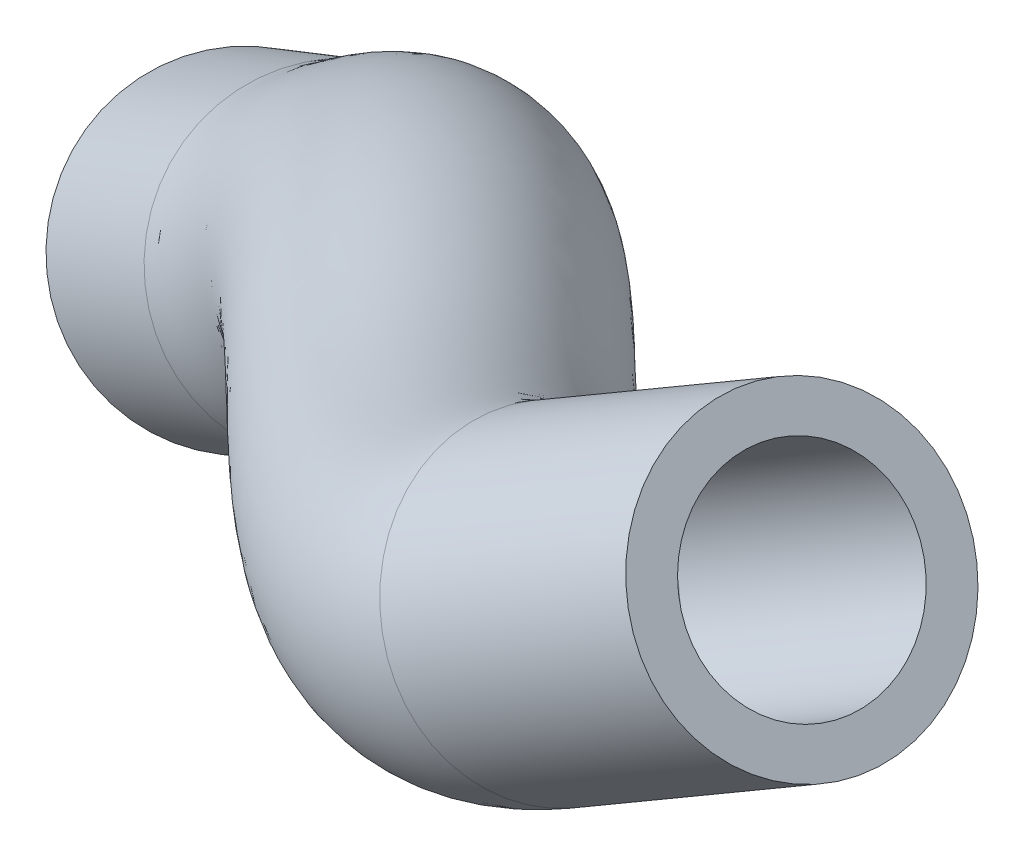
SolidWorks part; units mm, degrees
material "Silicon Rubber"
ref_plane "X-Y Datum" through (0, 0, 0) normal (0, 0, 1) x (1, 0, 0)
ref_plane "X-Z Datum" through (0, 0, 0) normal (0, 1, 0) x (1, 0, 0)
ref_plane "Y-Z Datum" through (0, 0, 0) normal (1, 0, 0) x (0, 0, -1)
sketch3d "3DSketch1"
  line L0 (-45.4816, -0.3823, -56.5666) -> (-26.4134, 13.1435, -46.636)
  line L1 (58.6408, 60.7321, 18.5097) -> (85.1939, 77.7553, 22.1439)
  line L2 (58.6408, 60.7321, 18.5097) -> (85.1939, 77.7553, 22.1439) construction
  line L3 (-28.7969, 11.4528, -47.8773) -> (-45.4816, -0.3823, -56.5666) construction
  line L4 (-26.4134, 13.1435, -46.636) -> (-45.4816, -0.3823, -56.5666) construction
  circle A1 centre (-28.7969, 11.4528, -47.8773) radius 8.2804 construction
  circle A12 centre (-45.4816, -0.3823, -56.5666) radius 9.525 construction
  circle A13 centre (-28.7969, 11.4528, -47.8773) radius 8.2804 construction
  circle A14 centre (-45.4816, -0.3823, -56.5666) radius 9.525 construction
  spline S0 degree 3 poles (-26.4134, 13.1435, -46.636) (-18.749, 18.5803, -42.6444) (-10.2444, 30.1331, -39.1286) (36.802, 46.0987, 8.6191) (52.8105, 56.9942, 17.7117) (58.6408, 60.7321, 18.5097) knots 0 0 0 0 0.436474 0.623537 1 1 1 1
  point P0 (3.3643, 33.9713, -24.8566)
  point P1 (0, 0, 0)
  point P8 (-22.5807, 15.8622, -44.6399)
  point P11 (-38.331, 4.6899, -52.8426)
  point P13 (-22.5807, 15.8622, -44.6399)
  point P16 (-38.331, 4.6899, -52.8426)
  dimension "D1" = 25.4
sweep "Sweep1" add path "3DSketch1" circular profile diameter 26.9875 parameters "D3"=26.9875
sweep "Cut-Sweep1" cut path "3DSketch1<2>" circular profile diameter 19.05 parameters "D3"=19.05
sketch3d "3DSketch1<2>" same geometry as "3DSketch1"
sketch3d "3DSketch2" [suppressed]
  circle A0 centre (15.1451, 20.3909, 0) radius 9.525 construction
  circle A1 centre (15.1451, 20.3909, 0) radius 9.525 construction
  circle A2 centre (58.6408, 60.7321, 18.5097) radius 9.525 construction
  circle A3 centre (58.6408, 60.7321, 18.5097) radius 9.525 construction
  point P2 (9.4657, 12.7443, 0)
  point P4 (9.4657, 12.7443, 0)
  point P7 (50.6749, 55.6251, 17.4194)
  point P9 (50.6749, 55.6251, 17.4194)
